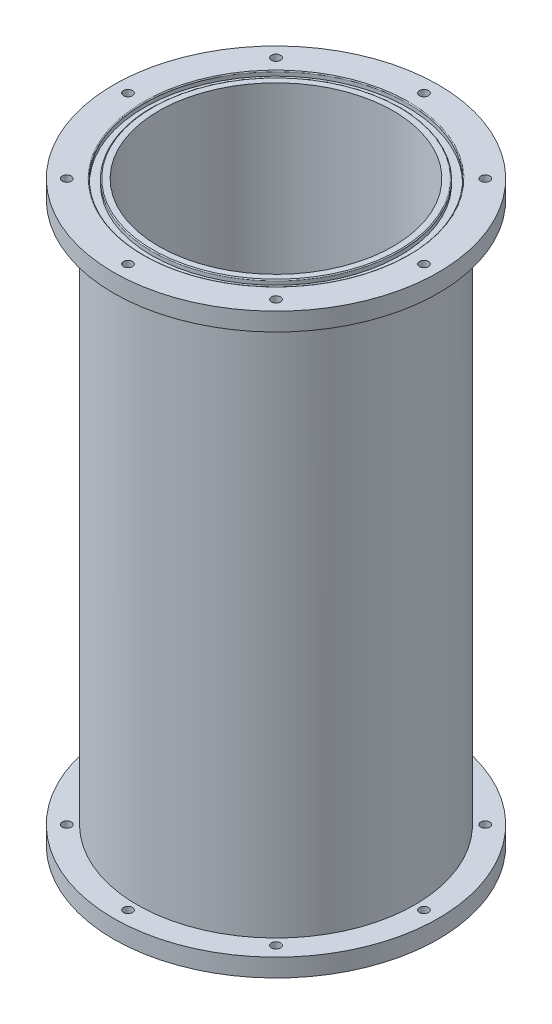
SolidWorks part; units mm, degrees
material "6061-T6 (SS)"
ref_plane "Front Plane" through (0, 0, 0) normal (0, 0, 1) x (1, 0, 0)
ref_plane "Top Plane" through (0, 0, 0) normal (0, 1, 0) x (1, 0, 0)
ref_plane "Right Plane" through (0, 0, 0) normal (1, 0, 0) x (0, 0, -1)
sketch "Sketch3" plane through (0, 0, 0) normal (0, 1, 0) x (1, 0, 0)
  circle A0 centre (0, 0) radius 32.5
  circle A1 centre (0, 0) radius 38.5
extrude "Boss-Extrude3" add sketch "Sketch3" along normal blind 160
sketch "Sketch5" plane through (0, 0, 0) normal (0, -1, 0) x (1, 0, 0)
  circle A0 centre (0, 0) radius 45
  circle A1 centre (0, 0) radius 32.5
  circle A2 centre (0, 0) radius 35.6743
  circle A3 centre (0, 0) radius 36.7411
  circle A4 centre (0, 0) radius 34.6075
  circle M1 centre (0, 0) radius 38.5
extrude "Cut-Extrude1" cut sketch "Sketch5" against normal blind 1.4224 contours A3 A2 | A2 A4 region at (-34.6653, 0, 0) region at (-35.7019, 0, 0)
extrude "Boss-Extrude5" add sketch "Sketch5<4>" against normal blind 5 contours A0 M1 region at (-43.7272, 0, 0)
sketch "Sketch5<4>" plane through (0, 0, 0) normal (0, -1, 0) x (1, 0, 0) same geometry as "Sketch5"
sketch "Sketch7" plane through (0, 5, 0) normal (0, 1, 0) x (1, 0, 0)
  circle A3 centre (0, 41.75) radius 1.55
  circle A4 centre (29.5217, 29.5217) radius 1.55
  circle A5 centre (41.75, 0) radius 1.55
  circle A6 centre (29.5217, -29.5217) radius 1.55
  circle A7 centre (0, -41.75) radius 1.55
  circle A8 centre (-29.5217, -29.5217) radius 1.55
  circle A9 centre (-41.75, 0) radius 1.55
  circle A10 centre (-29.5217, 29.5217) radius 1.55
  point P20 (0, 0)
  dimension "D1" = 8
extrude "Cut-Extrude2" cut sketch "Sketch7" against normal blind 5
sketch "Sketch9" plane through (0, 160, 0) normal (0, 1, 0) x (1, 0, 0)
  circle A0 centre (0, 0) radius 32.5
  circle A1 centre (0, 0) radius 38.5
extrude "Cut-Extrude3" cut sketch "Sketch9" against normal blind 80
mirror "Mirror7" about plane through (0, 80, 0) normal (0, 1, 0) of "Boss-Extrude3", "Cut-Extrude1", "Boss-Extrude5", "Cut-Extrude2"
extrude "Cut-Extrude6" cut sketch "Sketch5<7>" against normal blind 1.4224 contours A3 A2 | A2 A4 region at (-34.6653, 0, 0) region at (-35.7019, 0, 0)
sketch "Sketch5<7>" plane through (0, 0, 0) normal (0, -1, 0) x (1, 0, 0) same geometry as "Sketch5"
sketch "Sketch10" plane through (0, 160, 0) normal (0, 1, 0) x (1, 0, 0)
  circle A0 centre (0, 0) radius 34.6075
  circle A1 centre (0, 0) radius 36.7411
extrude "Boss-Extrude6" add sketch "Sketch10" against normal up to surface (160 mm away) up to face at (0, 0, -36.7411)
sketch "Sketch11" plane through (0, 160, 0) normal (0, 1, 0) x (1, 0, 0)
  circle A0 centre (0, 0) radius 36.5633
  circle A1 centre (0, 0) radius 34.4043
extrude "Cut-Extrude7" cut sketch "Sketch11" against normal blind 1.27
sketch "Sketch12" plane through (0, 0, 0) normal (0, -1, 0) x (1, 0, 0)
  circle A0 centre (0, 0) radius 36.5633
  circle A1 centre (0, 0) radius 34.4043
extrude "Cut-Extrude8" cut sketch "Sketch12" against normal blind 1.27
sketch "Sketch15" plane through (0, 160, 0) normal (0, 1, 0) x (1, 0, 0)
  circle A0 centre (0, 0) radius 36.5633
  circle A1 centre (0, 0) radius 45
extrude "Boss-Extrude7" add sketch "Sketch15" against normal up to surface (5 mm away) up to face at (-29.5217, 155, -27.9717)
sketch "Sketch16" plane through (0, 0, 0) normal (0, -1, 0) x (1, 0, 0)
  circle A0 centre (0, 0) radius 36.5633
  circle A1 centre (0, 0) radius 45
extrude "Boss-Extrude8" add sketch "Sketch16" against normal up to surface (5 mm away) up to face at (-29.5217, 5, -27.9717)
fillet "Fillet1" radius 0.254 4 edges at (0, 160, 34.4043) (0, 160, 36.5633) (0, 0, -34.4043) (0, 0, -36.5633)
sketch "Sketch24" plane through (0, 0, 0) normal (0, -1, 0) x (1, 0, 0)
  circle A0 centre (41, 0) radius 1.5
  circle A1 centre (28.9914, -28.9914) radius 1.5
  circle A2 centre (0, -41) radius 1.5
  circle A3 centre (-28.9914, -28.9914) radius 1.5
  circle A4 centre (-41, 0) radius 1.5
  circle A5 centre (-28.9914, 28.9914) radius 1.5
  circle A6 centre (0, 41) radius 1.5
  circle A7 centre (28.9914, 28.9914) radius 1.5
  point P1 (41, 0)
  point P6 (28.9914, -28.9914)
  point P8 (0, -41)
  point P10 (-28.9914, -28.9914)
  point P12 (-41, 0)
  point P14 (-28.9914, 28.9914)
  point P16 (0, 41)
  point P18 (28.9914, 28.9914)
  point P20 (0, 0)
  dimension "D1" = 8
  dimension "D2" = 41
hole_wizard "M3 Tapped Hole2" positions "Sketch24" profile "Sketch26" tap size "M3" standard "ISO"
cosmetic thread "Hole Thread1" parameters "D2"=3
cosmetic thread "Hole Thread2" parameters "D2"=3
cosmetic thread "Hole Thread3" parameters "D2"=3
cosmetic thread "Hole Thread4" parameters "D2"=3
cosmetic thread "Hole Thread5" parameters "D2"=3
cosmetic thread "Hole Thread6" parameters "D2"=3
cosmetic thread "Hole Thread7" parameters "D2"=3
cosmetic thread "Hole Thread8" parameters "D2"=3
sketch "Sketch26" plane through (41, 0, 0) normal (1, 0, 0) x (0, 0, -1)
  line L0 (0, 0) -> (0, 5.7511)
  line L1 (0, 5.7511) -> (1.25, 5)
  line L2 (1.25, 5) -> (1.25, 0)
  line L5 (1.25, 0) -> (0, 0)
  line L10 (0, 5.7511) -> (-1.25, 5) construction
  line L11 (0, -6.35) -> (0, 107.95) construction
  dimension "Tap Drill Dia." = 2.5
  dimension "Tap Drill Depth" = 5
  dimension "Drill Angle" = 118
sketch "Sketch27" plane through (0, 160, 0) normal (0, 1, 0) x (1, 0, 0)
  circle A0 centre (41, 0) radius 1.5
  circle A1 centre (28.9914, -28.9914) radius 1.5
  circle A2 centre (0, -41) radius 1.5
  circle A3 centre (-28.9914, -28.9914) radius 1.5
  circle A4 centre (-41, 0) radius 1.5
  circle A5 centre (-28.9914, 28.9914) radius 1.5
  circle A6 centre (0, 41) radius 1.5
  circle A7 centre (28.9914, 28.9914) radius 1.5
  point P0 (41, 0)
  point P2 (28.9914, -28.9914)
  point P7 (0, -41)
  point P9 (-28.9914, -28.9914)
  point P11 (-41, 0)
  point P13 (-28.9914, 28.9914)
  point P15 (0, 41)
  point P17 (28.9914, 28.9914)
  point P19 (0, 0)
  dimension "D1" = 41
  dimension "D2" = 8
hole_wizard "M3 Tapped Hole3" positions "Sketch27" profile "Sketch28" tap size "M3" standard "ISO"
sketch "Sketch28" plane through (41, 160, 0) normal (1, 0, 0) x (0, 0, 1)
  line L0 (0, 0) -> (0, 5.7511)
  line L1 (0, 5.7511) -> (1.25, 5)
  line L2 (1.25, 5) -> (1.25, 0)
  line L5 (1.25, 0) -> (0, 0)
  line L10 (0, 5.7511) -> (-1.25, 5) construction
  line L11 (0, -6.35) -> (0, 107.95) construction
  dimension "Tap Drill Dia." = 2.5
  dimension "Tap Drill Depth" = 5
  dimension "Drill Angle" = 118
cosmetic thread "Hole Thread9" parameters "D1"=160, "D2"=3
cosmetic thread "Hole Thread10" parameters "D1"=160, "D2"=3
cosmetic thread "Hole Thread11" parameters "D1"=160, "D2"=3
cosmetic thread "Hole Thread12" parameters "D1"=160, "D2"=3
cosmetic thread "Hole Thread13" parameters "D1"=160, "D2"=3
cosmetic thread "Hole Thread14" parameters "D1"=160, "D2"=3
cosmetic thread "Hole Thread15" parameters "D1"=160, "D2"=3
cosmetic thread "Hole Thread16" parameters "D1"=160, "D2"=3
